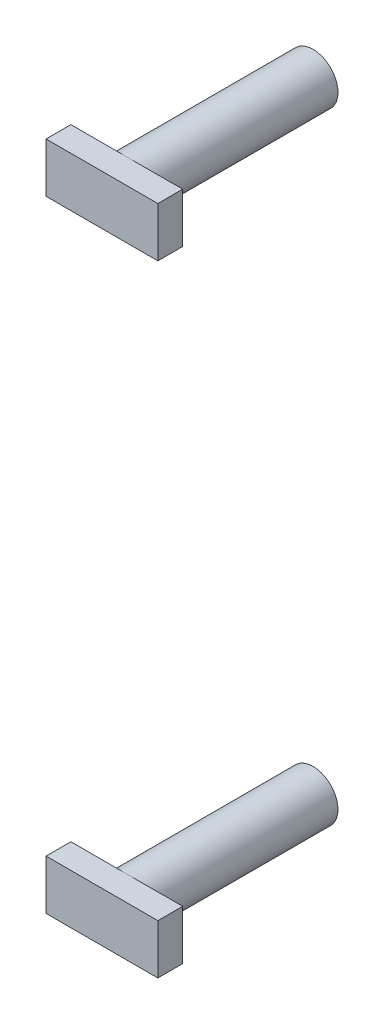
SolidWorks part; units mm, degrees
note: The reader was unsure of these and kept them because the rebuilt part matched: shared geometry of "Sketch1<3>".
ref_plane "FP" through (0, 0, 0) normal (0, 0, 1) x (1, 0, 0)
ref_plane "TP" through (0, 0, 0) normal (0, 1, 0) x (1, 0, 0)
ref_plane "RP" through (0, 0, 0) normal (1, 0, 0) x (0, 0, -1)
sketch "Sketch1" plane through (0, 0, 0) normal (0, 0, 1) x (1, 0, 0)
  line L0 (0, 0) -> (61.3468, 0) construction
  line L1 (14.5, -27) -> (23.5, -27)
  line L2 (14.5, -27) -> (14.5, -23)
  line L3 (14.5, -23) -> (23.5, -23)
  line L4 (23.5, -27) -> (23.5, -23)
  line L5 (14.5, -32) -> (14.5, 32) construction
  line L7 (14.5, 27) -> (14.5, 23)
  line L8 (14.5, 27) -> (23.5, 27)
  line L9 (23.5, 27) -> (23.5, 23)
  line L10 (14.5, 23) -> (23.5, 23)
  circle A0 centre (19, -25) radius 2 construction
  circle A1 centre (19, -25) radius 2
  circle A2 centre (19, 25) radius 2 construction
  circle A3 centre (19, 25) radius 2
  point P19 (0, 0)
  point P20 (0, 0)
  point P21 (0, 0)
  point P22 (0, 0)
  point P23 (0, 0)
  dimension "D1" = 2.5
extrude "Boss-Extrude1" add sketch "Sketch1" against normal blind 15 contours A1 | A3
extrude "Boss-Extrude2" add sketch "Sketch1<3>" along normal blind 2 contours A1 | L3 L4 L1 L2 | A3 | L8 L9 L10 L7
sketch "Sketch1<3>" plane through (0, 0, 0) normal (0, 0, 1) x (1, 0, 0) same geometry as "Sketch1"
